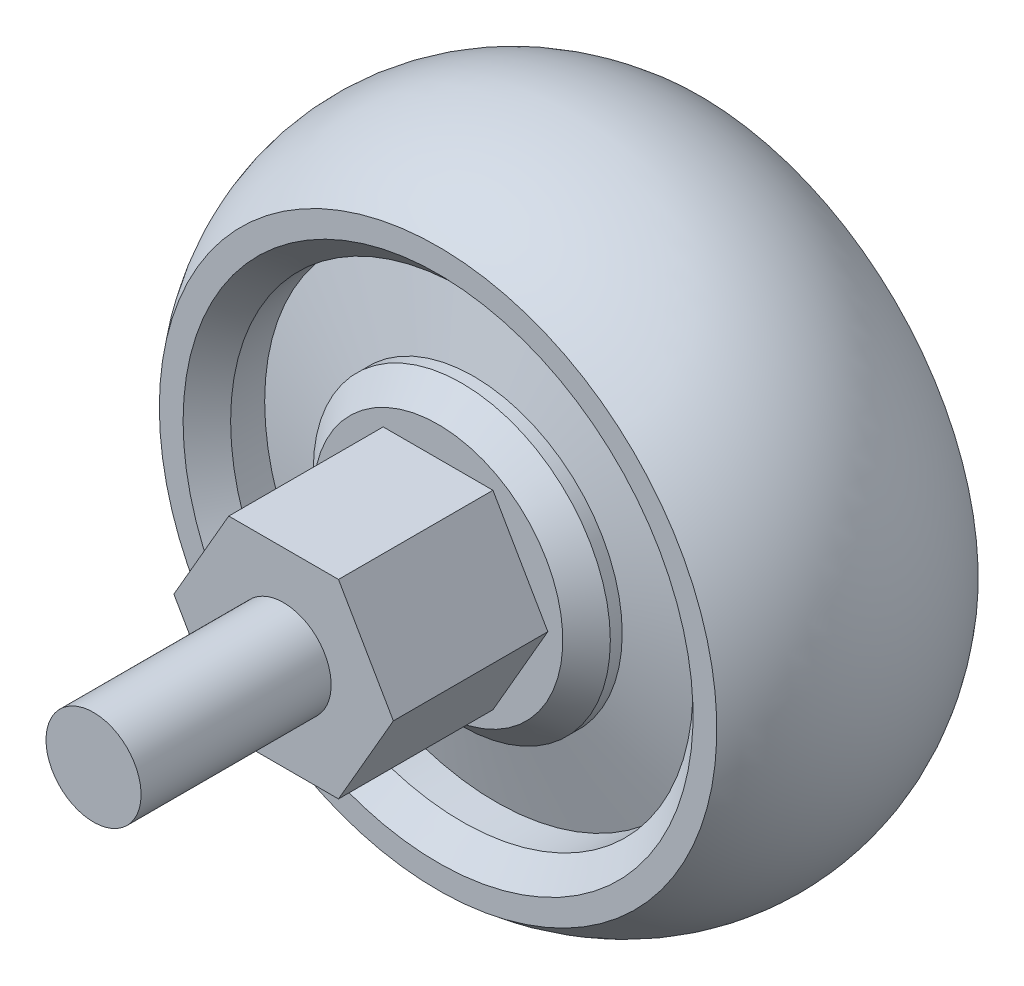
SolidWorks part; units mm, degrees
material "1345 Alloy"
ref_plane "Front Plane" through (0, 0, 0) normal (0, 0, 1) x (1, 0, 0)
ref_plane "Top Plane" through (0, 0, 0) normal (0, 1, 0) x (1, 0, 0)
ref_plane "Right Plane" through (0, 0, 0) normal (1, 0, 0) x (0, 0, -1)
sketch "Sketch1" plane through (0, 0, 0) normal (1, 0, 0) x (0, 0, -1)
  line L0 (0, 0) -> (-65.5623, 0) construction
  line L1 (13.97, 24.7161) -> (-13.97, 24.7161)
  line L2 (-13.97, 24.7161) -> (-13.97, 29.7961)
  line L3 (13.97, 29.7961) -> (13.97, 24.7161)
  line L4 (0, 0) -> (0, 34.925) construction
  line L5 (-7.791, 24.7161) -> (-10.16, 15.875)
  line L6 (-10.16, 15.875) -> (-30.48, 15.875)
  line L7 (-30.48, 15.875) -> (-30.48, 5.08)
  line L8 (-30.48, 5.08) -> (-50.8, 5.08)
  line L9 (-50.8, 5.08) -> (-50.8, 0)
  line L10 (-50.8, 0) -> (13.97, 0)
  line L11 (13.97, 0) -> (13.97, 15.875)
  line L12 (13.97, 15.875) -> (10.16, 15.875)
  line L13 (10.16, 15.875) -> (7.791, 24.7161)
  line L14 (-7.791, 24.7161) -> (7.791, 24.7161)
  arc A0 (-13.97, 29.7961) -> (13.97, 29.7961) centre (0, 13.335) cw
  point P20 (0, 24.7161)
  dimension "D4" = 21.59
  dimension "D1" = 27.94
  dimension "D2" = 69.85
  dimension "D3" = 5.08
  dimension "D5" = 15
  dimension "D6" = 31.75
  dimension "D7" = 20.32
  dimension "D8" = 20.32
  dimension "D9" = 20.32
  dimension "D10" = 10.16
revolve "Revolve1" add sketch "Sketch1" angle 360 about L0 region at (0, 9.3568, 10.356)
revolve "Revolve2" add sketch "Sketch1<3>" angle 360 about L0 region at (0, 29.1414, 0)
sketch "Sketch1<3>" plane through (0, 0, 0) normal (1, 0, 0) x (0, 0, -1) same geometry as "Sketch1"
sketch "Sketch2" plane through (0, 0, 30.48) normal (0, 0, 1) x (1, 0, 0)
  line L1 (-5.8659, 10.16) -> (-11.7318, 0)
  line L2 (-11.7318, 0) -> (-5.8659, -10.16)
  line L3 (-5.8659, -10.16) -> (5.8659, -10.16)
  line L4 (5.8659, -10.16) -> (11.7318, 0)
  line L5 (11.7318, 0) -> (5.8659, 10.16)
  line L6 (5.8659, 10.16) -> (-5.8659, 10.16)
  circle A0 centre (0, 0) radius 10.16 construction
  circle A2 centre (0, 0) radius 15.875
  circle A3 centre (0, 0) radius 15.875
  dimension "D1" = 20.32
  dimension "D2" = 0
extrude "Cut-Extrude1" cut sketch "Sketch2" against normal up to surface (16.51 mm away) up to face at (-29.7961, 0, 13.97)
chamfer "Chamfer1" distance 2.54 angle 45 4 edges at (-24.7161, 0, -13.97) (-15.875, 0, -13.97) (-24.7161, 0, 13.97) (-15.875, 0, 13.97)
